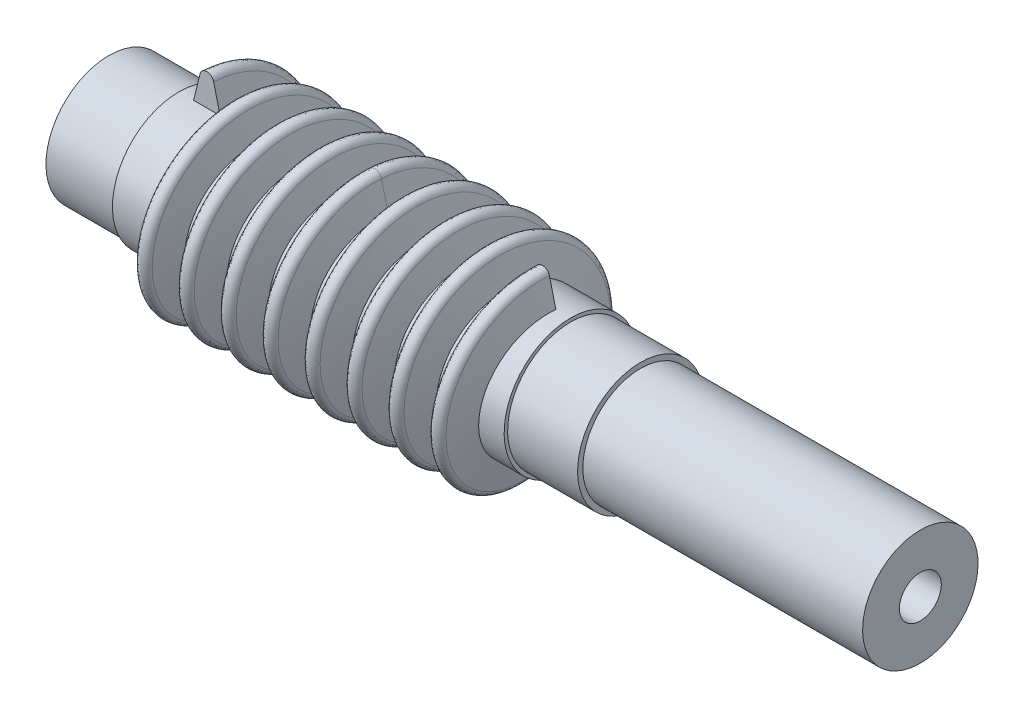
SolidWorks part; units mm, degrees
ref_plane "Alzado" through (0, 0, 0) normal (0, 0, 1) x (1, 0, 0)
ref_plane "Planta" through (0, 0, 0) normal (0, 1, 0) x (1, 0, 0)
ref_plane "Vista lateral" through (0, 0, 0) normal (1, 0, 0) x (0, 0, -1)
sketch "Croquis1" plane through (0, 0, 0) normal (0, 0, 1) x (1, 0, 0)
  line L0 (78, -11.75) -> (-38, -11.75)
  line L1 (-38, -11.75) -> (-38, -2.75)
  line L2 (-38, -2.75) -> (-28, -2.75)
  line L3 (-28, -2.75) -> (-28, -2.25)
  line L4 (-28, -2.25) -> (28, -2.25)
  line L5 (28, -2.25) -> (28, -2.75)
  line L6 (28, -2.75) -> (38, -2.75)
  line L7 (38, -2.75) -> (38, -3.5)
  line L8 (38, -3.5) -> (78, -3.5)
  line L9 (78, -3.5) -> (78, -11.75)
  dimension "D1" = 116
  dimension "D2" = 10
  dimension "D3" = 56
  dimension "D4" = 10
  dimension "D5" = 8.25
  dimension "D6" = 9.5
  dimension "D7" = 9
  dimension "D8" = 38
  dimension "D9" = 11.75
revolve "Revolución1" add sketch "Croquis1" angle 360 about L0
sketch "Croquis2" plane through (0, 0, 0) normal (1, 0, 0) x (0, 0, -1)
  circle A0 centre (0, -11.75) radius 9.5 construction
  circle A1 centre (0, -11.75) radius 9.5
curve "Hélice/Espiral1" pitch 6 height 24 radius 9.5 left hand yes centre (0, -11.75, 0) axis (1, 0, 0) start towards (0, 1, 0)
sketch "Croquis3" plane through (0, 0, 0) normal (0, 0, 1) x (1, 0, 0)
  line L0 (0, 1.25) -> (0, -5.2538) construction
  line L1 (28, -2.25) -> (-28, -2.25) construction
  line L2 (0.9705, 1.4911) -> (1.9, -2.25)
  line L3 (1.9, -2.25) -> (1.9, -2.95)
  line L4 (-1.9, -2.25) -> (-1.9, -2.95)
  line L5 (-0.9705, 1.4911) -> (-1.9, -2.25)
  line L6 (-1.9, -2.95) -> (1.9, -2.95)
  arc A0 (0.9705, 1.4911) -> (-0.9705, 1.4911) centre (0, 1.25) ccw
  dimension "D1" = 3.5
  dimension "D2" = 2
  dimension "D3" = 3.8
  dimension "D4" = 0.7
sweep "Barrer1" add profiles "Croquis3" path "Hélice/Espiral1"
sketch "Croquis4" plane through (0, 0, 0) normal (1, 0, 0) x (0, 0, -1)
  circle A0 centre (0, -11.75) radius 9.5 construction
  circle A1 centre (0, -11.75) radius 9.5
curve "Hélice/Espiral2" pitch 6 height 24 radius 9.5 left hand yes centre (0, -11.75, 0) axis (-1, 0, 0) start towards (0, 1, 0)
sketch "Croquis5" plane through (0, 0, 0) normal (0, 0, 1) x (1, 0, 0)
  line L5 (1.9, -2.25) -> (0.9705, 1.4911)
  line L6 (1.9, -2.95) -> (1.9, -2.25)
  line L7 (-1.9, -2.95) -> (1.9, -2.95)
  line L8 (-1.9, -2.25) -> (-1.9, -2.95)
  line L9 (-0.9705, 1.4911) -> (-1.9, -2.25)
  line L10 (1.9, -2.25) -> (0.9705, 1.4911)
  line L11 (1.9, -2.95) -> (1.9, -2.25)
  line L12 (-1.9, -2.95) -> (1.9, -2.95)
  line L13 (-1.9, -2.25) -> (-1.9, -2.95)
  line L14 (-0.9705, 1.4911) -> (-1.9, -2.25)
  arc A1 (0.9705, 1.4911) -> (-0.9705, 1.4911) centre (0, 1.25) ccw
  arc A2 (0.9705, 1.4911) -> (-0.9705, 1.4911) centre (0, 1.25) ccw
  dimension "D1" = 0
sweep "Barrer3" add profiles "Croquis5" path "Hélice/Espiral2"
sketch "Croquis6" plane through (78, 0, 0) normal (1, 0, 0) x (0, 0, -1)
  circle A0 centre (0, -11.75) radius 3
  dimension "D1" = 6
extrude "Cortar-Extruir1" cut sketch "Croquis6" against normal mid plane 10
